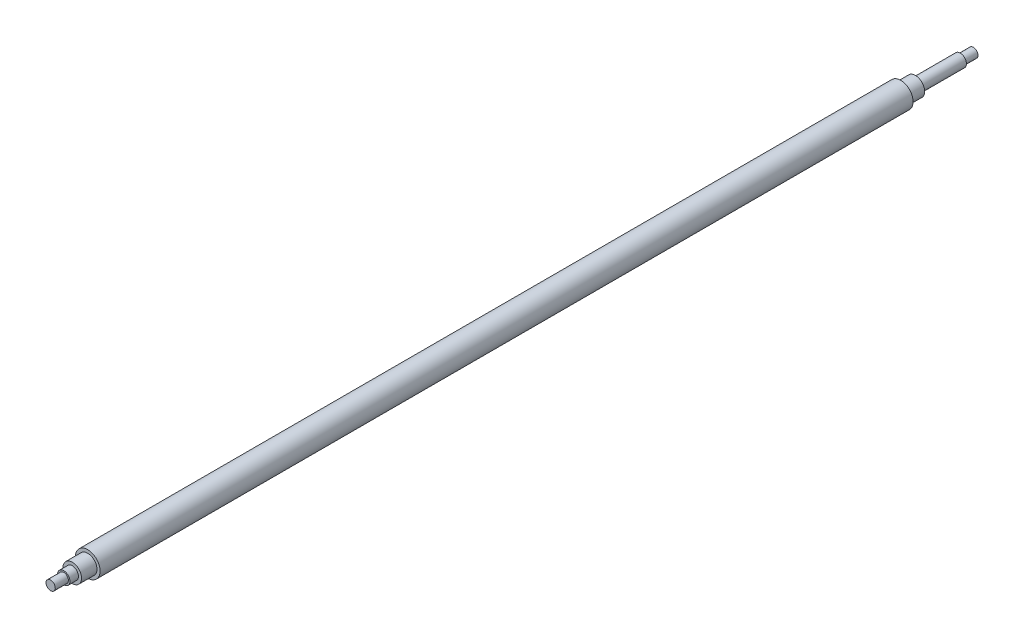
SolidWorks part; units mm, degrees
ref_plane "Piano frontale" through (0, 0, 0) normal (0, 0, 1) x (1, 0, 0)
ref_plane "Piano superiore" through (0, 0, 0) normal (0, 1, 0) x (1, 0, 0)
ref_plane "Piano destro" through (0, 0, 0) normal (1, 0, 0) x (0, 0, -1)
sketch "Schizzo2" plane through (0, 0, 0) normal (1, 0, 0) x (0, 0, -1)
  line L0 (0, 0) -> (0, 3)
  line L1 (0, 3) -> (8.5, 3)
  line L2 (8.5, 3) -> (8.5, 4)
  line L3 (8.5, 4) -> (14, 4)
  line L4 (14, 4) -> (14, 6)
  line L5 (14, 6) -> (24, 6)
  line L6 (24, 6) -> (24, 8)
  line L7 (24, 8) -> (550, 8)
  line L8 (550, 8) -> (550, 6)
  line L9 (550, 6) -> (559.5, 6)
  line L10 (559.5, 6) -> (559.5, 4)
  line L11 (597, 0) -> (0, 0)
  line L14 (597, 0) -> (597, 3)
  line L15 (0, 0) -> (351.0218, 0) construction
  line L16 (588.5, 3) -> (597, 3)
  line L17 (588.5, 4) -> (588.5, 3)
  line L18 (559.5, 4) -> (588.5, 4)
  point P33 (0, 0)
  dimension "D2" = 6
  dimension "D3" = 8
  dimension "D4" = 12
  dimension "D5" = 16
  dimension "D6" = 12
  dimension "D7" = 8
  dimension "D8" = 8.5
  dimension "D9" = 5.5
  dimension "D10" = 10
  dimension "D11" = 526
  dimension "D12" = 9.5
  dimension "D13" = 29
  dimension "D14" = 8.5
  dimension "D15" = 6
revolve "Rivoluzione2" add sketch "Schizzo2" angle 360 about L15
